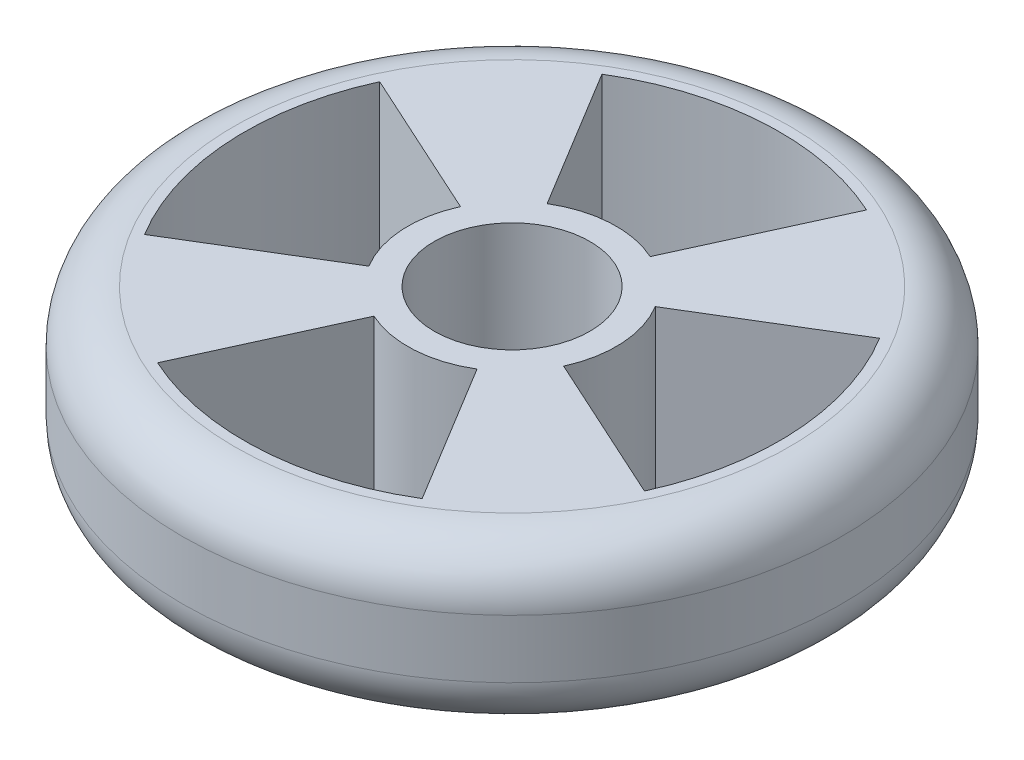
SolidWorks part; units mm, degrees
ref_plane "Front Plane" through (0, 0, 0) normal (0, 0, 1) x (1, 0, 0)
ref_plane "Top Plane" through (0, 0, 0) normal (0, 1, 0) x (1, 0, 0)
ref_plane "Right Plane" through (0, 0, 0) normal (1, 0, 0) x (0, 0, -1)
sketch "Sketch1" plane through (0, 0, 0) normal (0, 1, 0) x (1, 0, 0)
  circle A0 centre (0, 0) radius 50.8
extrude "Boss-Extrude1" add sketch "Sketch1" along normal blind 25 contours A0
fillet "Fillet2" radius 8 1 edges at (0, 25, 50.8)
fillet "Fillet3" radius 8 1 edges at (0, 0, 50.8)
sketch "Sketch2" plane through (0, 0, 0) normal (0, -1, 0) x (1, 0, 0)
  circle A0 centre (0, 0) radius 15
extrude "Boss-Extrude2" add sketch "Sketch2" along normal blind 5
sketch "Sketch3" plane through (0, 25, 0) normal (0, 1, 0) x (1, 0, 0)
  circle A0 centre (0, 0) radius 12
extrude "Cut-Extrude1" cut sketch "Sketch3" against normal blind 25
fillet "Fillet4" radius 8 1 edges at (0, 0, 15)
sketch "Sketch5" plane through (0, -5, 0) normal (0, -1, 0) x (1, 0, 0)
  line L0 (0, 8) -> (0, -7.0266) construction
  line L1 (-4.5258, 0) -> (8, 0) construction
  circle A0 centre (0, 0) radius 10.25 construction
  circle A1 centre (0, 0) radius 8 construction
  circle A2 centre (0, 8) radius 1.61
  circle A3 centre (0, -8) radius 1.61
  circle A4 centre (8, 0) radius 1.61
  circle A5 centre (-8, 0) radius 1.61
  circle A6 centre (0, 0) radius 4.2
extrude "Cut-Extrude2" cut sketch "Sketch5" against normal through all
sketch "Sketch6" plane through (0, 25, 0) normal (0, 1, 0) x (1, 0, 0)
  line L0 (30.1741, -28.1197) -> (-30.1741, 28.1197) construction
  line L1 (-31.2322, -29.2642) -> (31.2322, 29.2642) construction
  line L2 (1.0285, -41.2327) -> (-1.0285, 41.2327) construction
  line L3 (41.2456, 0) -> (-41.2456, 0) construction
  line L4 (6.6696, 14.6192) -> (17.1198, 37.5248)
  line L5 (-8.3374, 13.7365) -> (-21.4007, 35.2591)
  line L6 (13.7365, 8.3374) -> (35.2591, 21.4007)
  line L7 (14.6192, -6.6696) -> (37.5248, -17.1198)
  line L8 (8.3374, -13.7365) -> (21.4007, -35.2591)
  line L9 (-6.6696, -14.6192) -> (-17.1198, -37.5248)
  line L10 (-13.7365, -8.3374) -> (-35.2591, -21.4007)
  line L11 (-14.6192, 6.6696) -> (-37.5248, 17.1198)
  circle A0 centre (0, 0) radius 16.0687 construction
  circle A2 centre (0, 0) radius 41.2456 construction
  arc A3 (6.6696, 14.6192) -> (-8.3374, 13.7365) centre (0, 0) ccw
  circle A4 centre (0, 0) radius 42.8 construction
  arc A5 (17.1198, 37.5248) -> (-21.4007, 35.2591) centre (0, 0) ccw
  arc A6 (37.5248, -17.1198) -> (35.2591, 21.4007) centre (0, 0) ccw
  arc A7 (14.6192, -6.6696) -> (13.7365, 8.3374) centre (0, 0) ccw
  arc A8 (-17.1198, -37.5248) -> (21.4007, -35.2591) centre (0, 0) ccw
  arc A9 (-6.6696, -14.6192) -> (8.3374, -13.7365) centre (0, 0) ccw
  arc A10 (-37.5248, 17.1198) -> (-35.2591, -21.4007) centre (0, 0) ccw
  arc A11 (-14.6192, 6.6696) -> (-13.7365, -8.3374) centre (0, 0) ccw
  point P13 (0, 0)
  point P14 (0, 0)
  point P18 (0, 0)
  point P20 (0, 0)
  point P21 (0, 0)
  point P37 (0, 0)
  dimension "D1" = 4
extrude "Cut-Extrude3" cut sketch "Sketch6" against normal through all
sketch "Sketch7" plane through (0, 0, 0) normal (0, 1, 0) x (1, 0, 0)
  circle A0 centre (-8, 0) radius 3.4
  circle A1 centre (0, 8) radius 3.4
  circle A2 centre (8, 0) radius 3.4
  circle A3 centre (0, -8) radius 3.4
extrude "Cut-Extrude4" cut sketch "Sketch7" against normal blind 2.3
